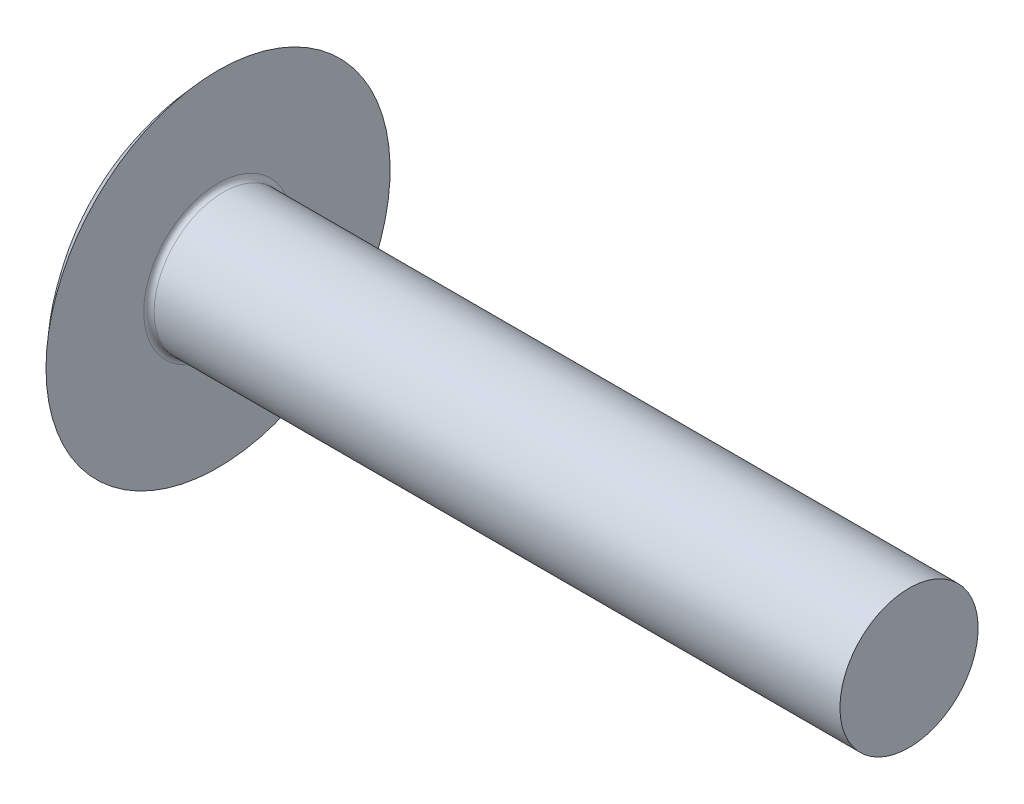
SolidWorks part; units mm, degrees
ref_plane "Front" through (0, 0, 0) normal (0, 0, 1) x (1, 0, 0)
ref_plane "Top" through (0, 0, 0) normal (0, 1, 0) x (1, 0, 0)
ref_plane "Right" through (0, 0, 0) normal (1, 0, 0) x (0, 0, -1)
sketch "Sketch1" plane through (0, 0, 0) normal (0, 0, 1) x (1, 0, 0)
  line L0 (-60.0944, 0) -> (17.9503, 0) construction
  line L1 (43.962, 0) -> (43.962, 4)
  line L2 (43.962, 4) -> (4.262, 4)
  line L3 (3.962, 4.3) -> (3.962, 9.96)
  line L4 (43.962, 0) -> (0, 0)
  arc A0 (3.962, 9.96) -> (0, 0) centre (14.5, 0) ccw
  arc A1 (4.262, 4) -> (3.962, 4.3) centre (4.262, 4.3) cw
  dimension "R" = 14.5
  dimension "r1" = 0.3
  dimension "d" = 8
  dimension "dk" = 19.92
  dimension "l" = 40
revolve "Base-Revolve" add sketch "Sketch1" angle 360 about L0
